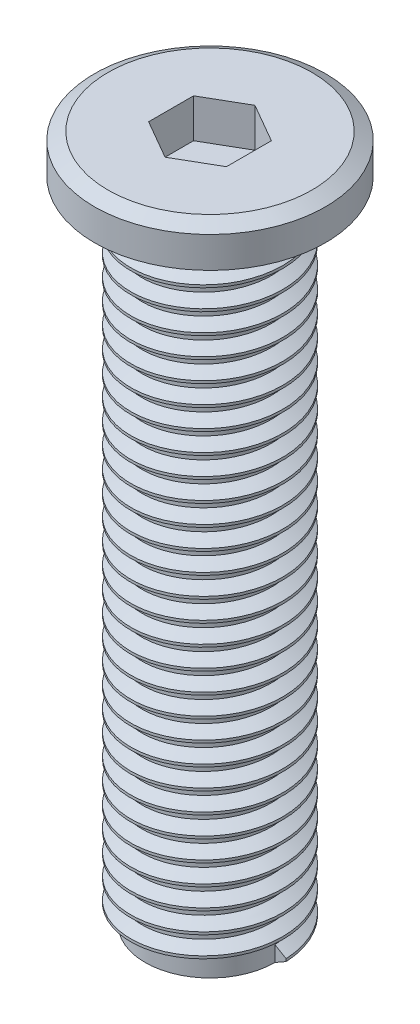
SolidWorks part; units mm, degrees
ref_plane "Front Plane" through (0, 0, 0) normal (0, 0, 1) x (1, 0, 0)
ref_plane "Top Plane" through (0, 0, 0) normal (0, 1, 0) x (1, 0, 0)
ref_plane "Right Plane" through (0, 0, 0) normal (1, 0, 0) x (0, 0, -1)
sketch "Sketch1" plane through (0, 0, 0) normal (0, 1, 0) x (1, 0, 0)
  circle A0 centre (0, 0) radius 4.45
  dimension "D1" = 8.9
extrude "Boss-Extrude1" add sketch "Sketch1" along normal blind 1.5
chamfer "Chamfer2" distance 0.3 angle 60 1 edges at (0, 1.5, 4.45)
sketch "Sketch8" plane through (0, 1.5, 0) normal (0, 1, 0) x (1, 0, 0)
  line L1 (0, 1.7321) -> (-1.5, 0.866)
  line L2 (-1.5, 0.866) -> (-1.5, -0.866)
  line L3 (-1.5, -0.866) -> (0, -1.7321)
  line L4 (0, -1.7321) -> (1.5, -0.866)
  line L5 (1.5, -0.866) -> (1.5, 0.866)
  line L6 (1.5, 0.866) -> (0, 1.7321)
  circle A0 centre (0, 0) radius 1.5 construction
  dimension "D1" = 3
  dimension "D2" = 1.5
extrude "Cut-Extrude1" cut sketch "Sketch8" against normal blind 3
sketch "Sketch3" plane through (0, 0, 0) normal (0, -1, 0) x (1, 0, 0)
  circle A0 centre (0, 0) radius 2.5
  dimension "D1" = 5
extrude "Boss-Extrude2" add sketch "Sketch3" along normal blind 25
thread "Thread1" pitch 0.8 profile "Thread Profile2" start angle 0, offset 0, length 24.4, pitch 0.8, diameter 5
ref_plane "Plane2" through (-2.5, 0, 0) normal (0, 0, 1) x (-1, 0, 0)
sketch "Thread Profile2" plane through (-2.5, 0, 0) normal (0, 0, 1) x (-1, 0, 0)
  line L0 (0, 0) -> (0, 0.8) construction
  line L1 (0, 0) -> (0.433, 0.25)
  line L2 (0.433, 0.25) -> (0.433, 0.35)
  line L3 (0.433, 0.35) -> (0, 0.6)
  line L4 (0.433, 0.3) -> (0, 0.3) construction
  line L11 (0, 0) -> (0, 0.6)
  point P2 (0, 0)
  dimension "Pitch" = 0.8
  dimension "Profile_Angle" = 60
  dimension "Profile_Land" = 0.1
  dimension "Profile_Height" = 0.433
